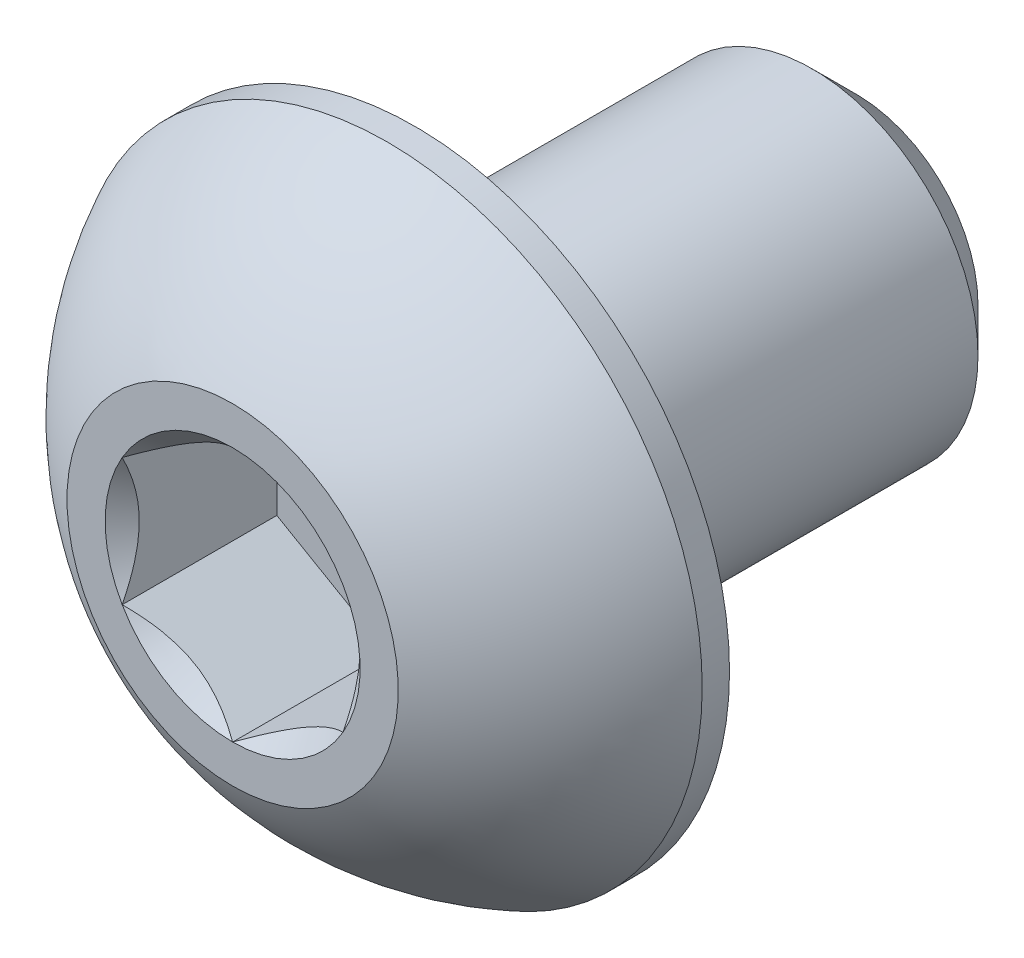
SolidWorks part; units mm, degrees
material "Alloy Steel"
ref_plane "Front Plane" through (0, 0, 0) normal (0, 0, 1) x (1, 0, 0)
ref_plane "Top Plane" through (0, 0, 0) normal (0, 1, 0) x (1, 0, 0)
ref_plane "Right Plane" through (0, 0, 0) normal (1, 0, 0) x (0, 0, -1)
sketch "Sketch1" plane through (0, 0, 0) normal (1, 0, 0) x (0, 0, -1)
  line L0 (-2.825, 0) -> (2.825, 0) construction
  line L1 (-1.175, 2.85) -> (-1.175, -2.85) construction
  line L2 (2.825, 1.5) -> (2.825, -1.5) construction
  line L3 (2.7937, 1.5541) -> (3.0437, 1.1211) construction
  line L4 (3.0437, 1.1211) -> (3.2937, 1.5541) construction
  line L5 (3.2937, 1.5541) -> (2.7937, 1.5541) construction
  line L6 (2.825, 1.5) -> (3.2625, 1.5) construction
  line L7 (3.0437, 1.5541) -> (3.0437, 1.5) construction
  line L8 (3.0437, 1.5) -> (3.0437, 1.1752) construction
  line L9 (3.0437, 1.1752) -> (3.0437, 1.1211) construction
  line L10 (3.0125, 1.1752) -> (3.075, 1.1752)
  line L11 (2.8094, 1.5271) -> (3.2781, 1.5271)
  line L12 (3.075, 1.1752) -> (3.2781, 1.5271)
  line L13 (3.0125, 1.1752) -> (2.8094, 1.5271)
  line L14 (-2.825, 1) -> (-2.825, -1) construction
  line L15 (2.825, 1.5) -> (-1.175, 1.5) construction
  point P3 (-1.175, 0)
  point P6 (-1.425, 0)
  point P21 (3.0437, 1.5271)
  point P24 (-1.4225, 2.85)
  point P25 (1.575, -1.5)
  point P26 (-2.825, 1.5)
  dimension "Head Height" = 1.65
  dimension "Length" = 4
  dimension "Head Dia" = 5.7
  dimension "Thread Dia" = 3
  dimension "Pitch" = 0.5
  dimension "D2" = 0.0625
  dimension "Drive Size" = 2
  dimension "D1" = 1.4
  dimension "D3" = 0.2475
  dimension "D4" = 1.25
sketch "Sketch2" plane through (0, 0, 0) normal (1, 0, 0) x (0, 0, -1)
  line L0 (-2.825, 0) -> (2.825, 0)
  line L1 (2.825, 0) -> (2.825, 1.1)
  line L2 (2.825, 1.5) -> (2.825, -1.5) construction
  line L3 (2.825, 1.1) -> (2.425, 1.5)
  line L4 (2.425, 1.5) -> (-1.175, 1.5)
  line L5 (-1.175, 2.85) -> (-1.175, -2.85) construction
  line L6 (-1.175, 1.5) -> (-1.175, 2.85)
  line L7 (-1.175, 2.85) -> (-1.4225, 2.85)
  line L8 (2.825, 1.5) -> (3.2625, 1.5) construction
  line L9 (-2.825, 0) -> (-2.825, 1.5)
  arc A0 (-2.825, 1.5) -> (-1.4225, 2.85) centre (-0.0302, 0) cw
  dimension "D1" = 0.4
  dimension "D2" = 45
revolve "Revolve1" add sketch "Sketch2" angle 360 about L0
sketch "Sketch3" plane through (0, 0, 2.825) normal (0, 0, 1) x (1, 0, 0)
  line L1 (0, 1.1547) -> (-1, 0.5774)
  line L2 (-1, 0.5774) -> (-1, -0.5774)
  line L3 (-1, -0.5774) -> (0, -1.1547)
  line L4 (0, -1.1547) -> (1, -0.5774)
  line L5 (1, -0.5774) -> (1, 0.5774)
  line L6 (1, 0.5774) -> (0, 1.1547)
  circle A0 centre (0, 0) radius 1 construction
  dimension "D1" = 2
extrude "Cut-Extrude1" cut sketch "Sketch3" against normal up to vertex (1.4 mm away) up to point (0, 0, 1.425)
sketch "Sketch4" plane through (0, 0, 2.825) normal (0, 0, 1) x (1, 0, 0)
  circle A0 centre (0, 0) radius 1.1547
extrude "Cut-Extrude2" cut sketch "Sketch4" against normal blind 10 draft 45
split "Split1" [suppressed] bodies to split 106
sketch "Sketch5" [suppressed] plane through (0, 0, -2.825) normal (0, 0, -1) x (-1, 0, 0)
  circle A0 centre (0, 0) radius 1.5 construction
  circle A1 centre (0, 0) radius 1.5
curve "Helix/Spiral1" [suppressed] pitch 0.5 height 4.5 turns 9
sketch "Sketch6" [suppressed] plane through (0, 0, 0) normal (1, 0, 0) x (0, 0, -1)
  line L0 (3.0125, 1.1752) -> (3.075, 1.1752) construction
  line L1 (3.0125, 1.1752) -> (2.8094, 1.5271) construction
  line L2 (2.8094, 1.5271) -> (3.2781, 1.5271) construction
  line L3 (3.075, 1.1752) -> (3.2781, 1.5271) construction
  line L4 (3.0125, 1.1752) -> (3.075, 1.1752)
  line L5 (3.0125, 1.1752) -> (2.8094, 1.5271)
  line L6 (2.8094, 1.5271) -> (3.2781, 1.5271)
  line L7 (3.075, 1.1752) -> (3.2781, 1.5271)
sweep "Cut-Sweep1" [suppressed] cut profiles "Sketch6" path "Helix/Spiral1"
sketch "Sketch7" [suppressed] plane through (0, 0, 1.175) normal (0, 0, -1) x (-1, 0, 0)
  circle A1 centre (0, 0) radius 1.5
  circle A2 centre (0, 0) radius 1.5
  dimension "D1" = 0
extrude "Boss-Extrude1" [suppressed] add sketch "Sketch7" along normal blind 10 draft 30
equation "\"D2@Sketch1\" = \"Pitch@Sketch1\" / 8"
equation "\"D1@Sketch1\"=\"Drive Size@Sketch1\"*.7"
equation "\"D3@Sketch1\"=\"Head Height@Sketch1\"*.15"
equation "\"D1@Sketch2\"=\"Pitch@Sketch1\"*.8"
equation "\"D1@Sketch3\"=\"Drive Size@Sketch1\""
equation "\"D4@Helix/Spiral1\"=\"Pitch@Sketch1\""
equation "\"D3@Helix/Spiral1\"=\"Length@Sketch1\"+\"Pitch@Sketch1\""
equation "\"D4@Sketch1\"=\"Pitch@Sketch1\"*2.5"
